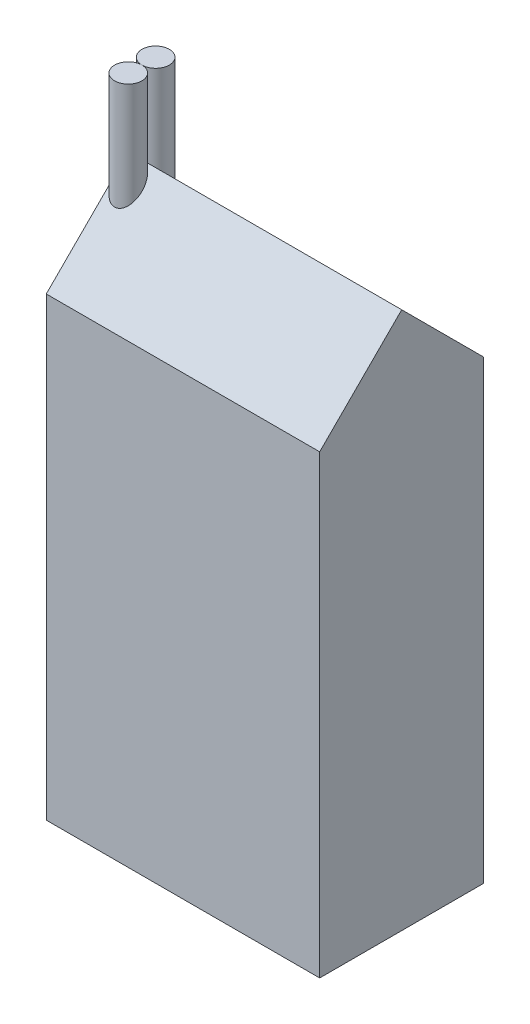
SolidWorks part; units mm, degrees
ref_plane "Alzado" through (0, 0, 0) normal (0, 0, 1) x (1, 0, 0)
ref_plane "Planta" through (0, 0, 0) normal (0, 1, 0) x (1, 0, 0)
ref_plane "Vista lateral" through (0, 0, 0) normal (1, 0, 0) x (0, 0, -1)
sketch "Croquis1" plane through (0, 0, 0) normal (0, 0, 1) x (1, 0, 0)
  line L1 (-15, -30) -> (15, -30)
  line L2 (-15, -30) -> (-15, 30)
  line L3 (-15, 30) -> (15, 30)
  line L4 (15, -30) -> (15, 30)
  line L5 (-15, -30) -> (15, 30) construction
  line L6 (-15, 30) -> (15, -30) construction
  point P0 (0, 0)
  dimension "D1" = 30
  dimension "D2" = 60
extrude "Saliente-Extruir1" add sketch "Croquis1" along normal mid plane 18
chamfer "Chaflán1" distance 10 angle 45 2 edges at (0, 30, -9) (0, 30, 9)
sketch "Croquis2" plane through (0, 0, 0) normal (0, 1, 0) x (1, 0, 0)
  line L0 (0, 0) -> (-21.2398, 0) construction
  line L1 (-15, 1.5) -> (-15, -0.8473) construction
  line L3 (-15, 0) -> (-15, 9) construction
  circle A0 centre (-13.5, 1.5) radius 1.5
  circle A1 centre (-13.5, -1.5) radius 1.5
  point P5 (0, 0)
  point P8 (-13.9851, 1.5)
  dimension "D1" = 3
extrude "Saliente-Extruir4" add sketch "Croquis2" along normal blind 38 separate body contours A0 | A1
